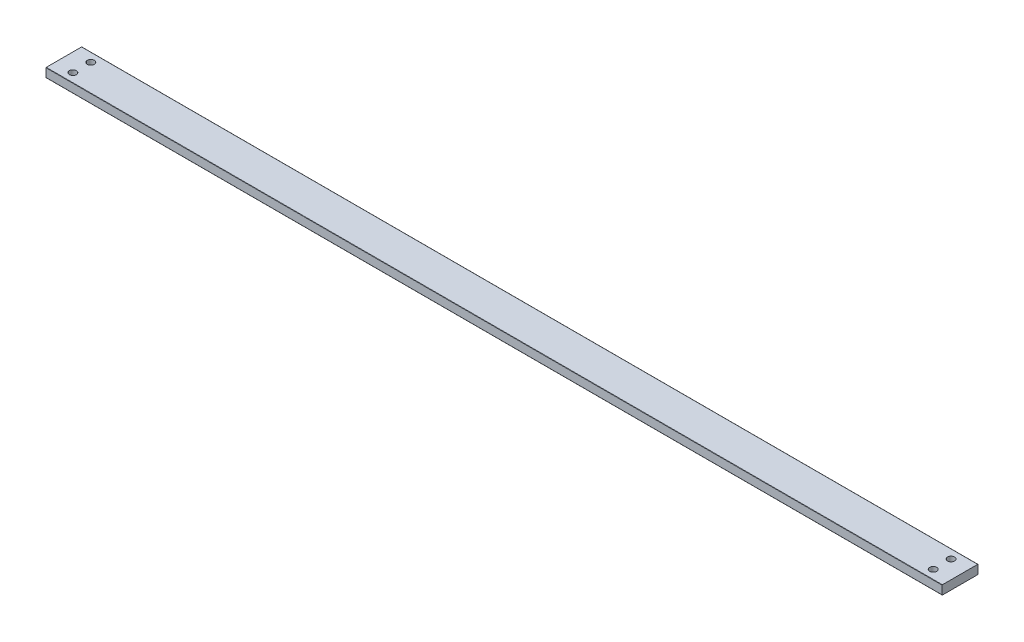
SolidWorks part; units mm, degrees
ref_plane "Front Plane" through (0, 0, 0) normal (0, 0, 1) x (1, 0, 0)
ref_plane "Top Plane" through (0, 0, 0) normal (0, 1, 0) x (1, 0, 0)
ref_plane "Right Plane" through (0, 0, 0) normal (1, 0, 0) x (0, 0, -1)
sketch "Sketch1" plane through (0, 0, 0) normal (0, 1, 0) x (1, 0, 0)
  line L1 (317.5, -12.7) -> (-317.5, -12.7)
  line L2 (317.5, -12.7) -> (317.5, 12.7)
  line L3 (317.5, 12.7) -> (-317.5, 12.7)
  line L4 (-317.5, -12.7) -> (-317.5, 12.7)
  line L5 (317.5, -12.7) -> (-317.5, 12.7) construction
  line L6 (317.5, 12.7) -> (-317.5, -12.7) construction
  point P0 (0, 0)
  dimension "Length" = 635
  dimension "Width" = 25.4
sketch "Sketch2" plane through (0, 0, 0) normal (1, 0, 0) x (0, 0, -1)
  line L0 (12.7, 3.175) -> (12.7, -3.175) construction
  point P2 (12.7, 0)
  dimension "Thickness" = 6.35
sketch "Sketch3" plane through (0, 0, 0) normal (0, 1, 0) x (1, 0, 0)
  line L1 (-317.5, 12.7) -> (317.5, 12.7)
  line L2 (-317.5, 12.7) -> (-317.5, -12.7)
  line L3 (-317.5, -12.7) -> (317.5, -12.7)
  line L4 (317.5, 12.7) -> (317.5, -12.7)
extrude "Boss-Extrude1" add sketch "Sketch3" against normal up to vertex (3.175 mm away) and the other way up to vertex (3.175 mm away) up to point (0, -3.175, -12.7) other way up to point (0, 3.175, -12.7)
fillet "Fillet1" radius 0.2095 4 edges at (0, -3.175, 12.7) (0, -3.175, -12.7) (0, 3.175, -12.7) (0, 3.175, 12.7)
sketch "Sketch4" plane through (0, 3.175, 0) normal (0, 1, 0) x (1, 0, 0)
  line L0 (-317.5, 0) -> (-304.8, 0) construction
  line L1 (-317.5, 12.4904) -> (-317.5, -12.4904) construction
  line L2 (317.5, 0) -> (304.8, 0) construction
  line L3 (317.5, -12.4904) -> (317.5, 12.4904) construction
  line L4 (-304.8, 0) -> (-304.8, 6.35) construction
  line L5 (-304.8, 0) -> (-304.8, -6.35) construction
  line L6 (304.8, 0) -> (304.8, 6.35) construction
  line L7 (304.8, 0) -> (304.8, -6.35) construction
hole_wizard "#10 Clearance Hole1" positions "Sketch5" profile "Sketch6" hole size "#10" standard "ANSI Inch" end condition through all
sketch "Sketch5" plane through (0, 3.175, 0) normal (0, 1, 0) x (1, 0, 0)
  point P0 (304.8, -6.35)
  point P3 (-304.8, -6.35)
  point P11 (304.8, 6.35)
  point P14 (-304.8, 6.35)
sketch "Sketch6" plane through (304.8, 3.175, 6.35) normal (1, 0, 0) x (0, 0, 1)
  line L0 (0, 0) -> (0, 6.35)
  line L1 (0, 6.35) -> (2.4892, 6.35)
  line L2 (2.4892, 6.35) -> (2.4892, 0)
  line L5 (2.4892, 0) -> (0, 0)
  line L11 (0, -6.35) -> (0, 107.95) construction
  dimension "Thru Hole Dia." = 4.9784
  dimension "Thru Hole Depth" = 6.35
equation "\"D1@Fillet1\" = \"Thickness@Sketch2\" * .033"
